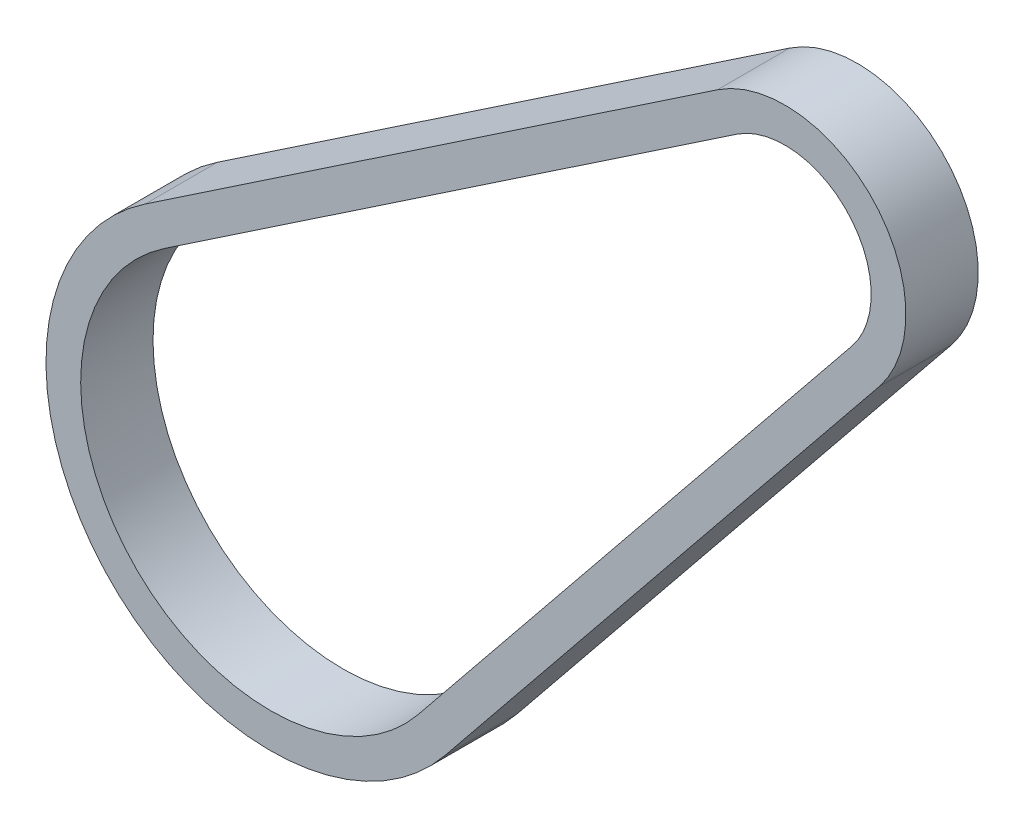
SolidWorks part; units mm, degrees
material "Rubber"
ref_plane "Front Plane" through (0, 0, 0) normal (0, 0, 1) x (1, 0, 0)
ref_plane "Top Plane" through (0, 0, 0) normal (0, 1, 0) x (1, 0, 0)
ref_plane "Right Plane" through (0, 0, 0) normal (1, 0, 0) x (0, 0, -1)
sketch "Sketch2" plane through (0, 0, 0) normal (0, 0, 1) x (1, 0, 0)
  line L0 (0, 0) -> (1, 0) construction
  line L1 (0, 0) -> (0, 1) construction
  line L2 (5.5674, -4.5054) -> (-24.4279, -41.5712)
  line L3 (-43.5589, -20.6763) -> (-3.9981, 5.9421)
  arc A0 (-3.9981, 5.9421) -> (5.5674, -4.5054) centre (0, 0) cw
  arc A1 (-24.4279, -41.5712) -> (-43.5589, -20.6763) centre (-35.5626, -32.5605) cw
extrude "Extrude-Thin1" add sketch "Sketch2" against normal blind 5 thin thin type two direction wall 1.2 second wall 1.2
